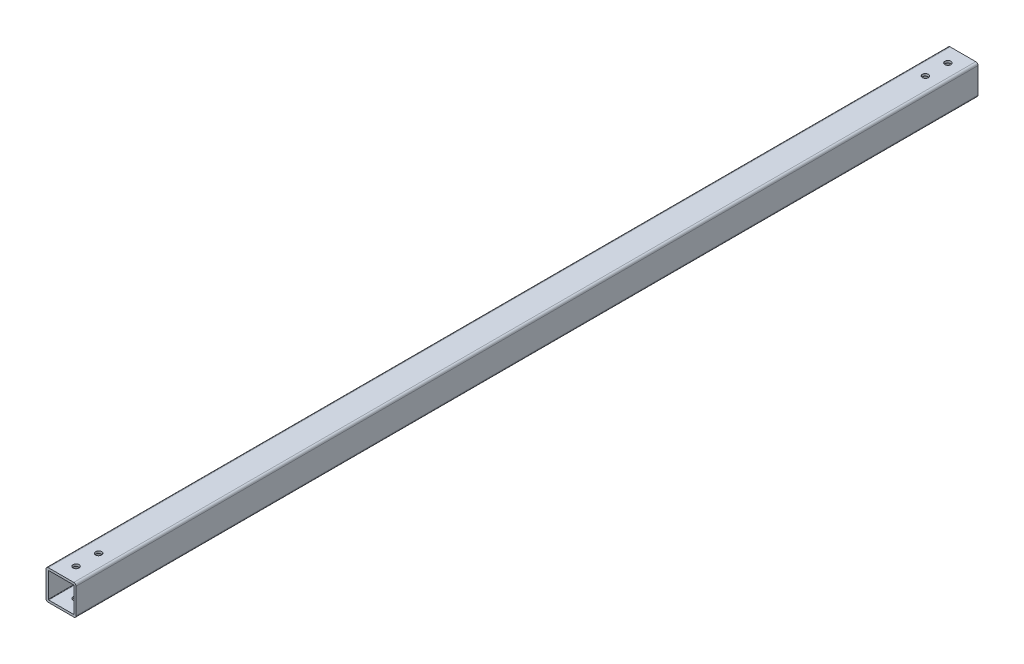
SolidWorks part; units mm, degrees
ref_plane "Front Plane" through (0, 0, 0) normal (0, 0, 1) x (1, 0, 0)
ref_plane "Top Plane" through (0, 0, 0) normal (0, 1, 0) x (1, 0, 0)
ref_plane "Right Plane" through (0, 0, 0) normal (1, 0, 0) x (0, 0, -1)
sketch "Sketch1" plane through (0, 0, 0) normal (0, 0, 1) x (1, 0, 0)
  line L1 (-20, 20) -> (20, 20)
  line L2 (-20, 20) -> (-20, -20)
  line L3 (-20, -20) -> (20, -20)
  line L4 (20, 20) -> (20, -20)
  line L5 (-20, 20) -> (20, -20) construction
  line L6 (-20, -20) -> (20, 20) construction
  point P0 (0, 0)
  dimension "D1" = 40
  dimension "D2" = 40
extrude "Extrude-Thin1" add sketch "Sketch1" along normal blind 1200 thin thin type one direction reverse wall 3
fillet "Fillet1" radius 0.5 4 edges at (-17, -17, 600) (-17, 17, 600) (17, 17, 600) (17, -17, 600)
fillet "Fillet2" radius 3 4 edges at (20, -20, 600) (-20, -20, 600) (20, 20, 600) (-20, 20, 600)
hole_wizard "Ø8.0 (8) Diameter Hole1" positions "Sketch4" profile "Sketch3" hole size "Ø8.0" standard "ANSI Metric" end condition through all
sketch "Sketch4" plane through (0, 20, 0) normal (0, 1, 0) x (1, 0, 0)
  line L0 (0, -1200) -> (0, 0) construction
  line L1 (17, -1200) -> (-17, -1200) construction
  point P10 (0, -1180)
  point P12 (0, -20)
  dimension "D1" = 20
  dimension "D2" = 20
sketch "Sketch3" plane through (0, 20, 1180) normal (1, 0, 0) x (0, 0, 1)
  line L0 (0, 0) -> (0, 40)
  line L1 (0, 40) -> (4, 40)
  line L2 (4, 40) -> (4, 0)
  line L5 (4, 0) -> (0, 0)
  line L11 (0, -6.35) -> (0, 107.95) construction
  dimension "Thru Hole Dia." = 8
  dimension "Thru Hole Depth" = 40
sketch "Sketch5" plane through (0, 20, 0) normal (0, 1, 0) x (1, 0, 0)
  line L0 (172.9723, -600) -> (-208.9573, -600) construction
  line L1 (17, 0) -> (-17, 0) construction
  line L2 (20, 0) -> (20, -1200) construction
  circle A0 centre (0, -1150) radius 4
  circle A1 centre (0, -1180) radius 4 construction
  circle A2 centre (0, -50) radius 4
  dimension "D1" = 30
  dimension "D2" = 8
  dimension "D3" = 600
  dimension "D4" = 20
extrude "Cut-Extrude1" cut sketch "Sketch5" against normal through all
equation "\"a\"= \"Beam Profile@Plasma Beta.Assembly\""
equation "\"b\"= 3"
equation "\"L\"= \"Width@Plasma Beta.Assembly\""
equation "\"D2@Sketch1\"=\"a\""
equation "\"D1@Sketch1\"=\"a\""
equation "\"D1@Extrude-Thin1\"=\"L\""
equation "\"D5@Extrude-Thin1\"=\"b\""
equation "\"D1@Fillet2\"=\"b\""
